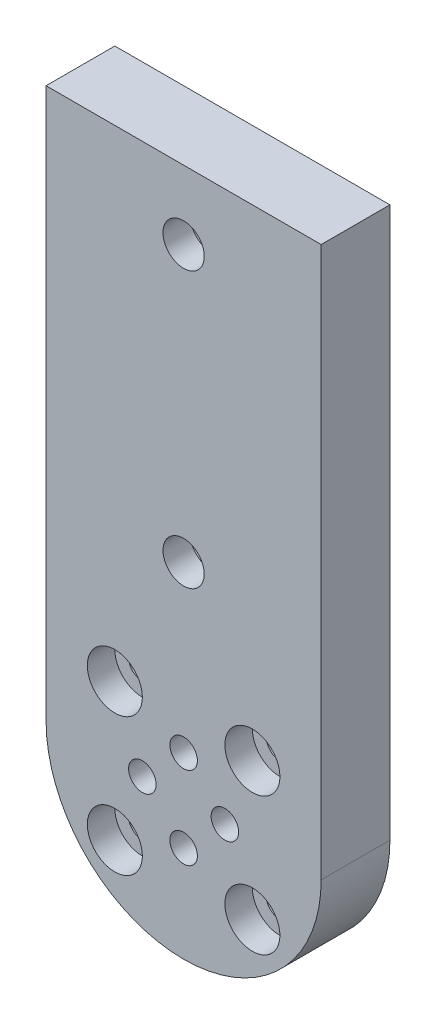
SolidWorks part; units mm, degrees
material "1060 Alloy"
ref_plane "Front Plane" through (0, 0, 0) normal (0, 0, 1) x (1, 0, 0)
ref_plane "Top Plane" through (0, 0, 0) normal (0, 1, 0) x (1, 0, 0)
ref_plane "Right Plane" through (0, 0, 0) normal (1, 0, 0) x (0, 0, -1)
sketch "Sketch2" plane through (0, 0, 0) normal (0, 0, 1) x (1, 0, 0)
  line L0 (-10, 0) -> (-10, 40)
  line L1 (-5, 5) -> (5, 5) construction
  line L2 (-5, 5) -> (-5, -5) construction
  line L3 (-5, -5) -> (5, -5) construction
  line L4 (5, 5) -> (5, -5) construction
  line L5 (-5, 5) -> (5, -5) construction
  line L6 (-5, -5) -> (5, 5) construction
  line L7 (10, 0) -> (10, 40)
  line L8 (-10, 40) -> (10, 40)
  line L9 (0, 40) -> (0, -10) construction
  circle A0 centre (0, 0) radius 10
  circle A1 centre (-5, 5) radius 1
  circle A2 centre (5, 5) radius 1
  circle A3 centre (-5, -5) radius 1
  circle A4 centre (5, -5) radius 1
  circle A5 centre (0, 35) radius 1.5
  circle A6 centre (0, 15) radius 1.5
  dimension "D4" = 2
  dimension "D5" = 2
  dimension "D6" = 2
  dimension "D7" = 2
  dimension "D9" = 3
  dimension "D10" = 3
  dimension "D13" = 20
  dimension "D2" = 10
  dimension "D3" = 10
  dimension "D8" = 40
  dimension "D11" = 20
  dimension "D12" = 5
extrude "Boss-Extrude1" add sketch "Sketch2" along normal blind 5 contours A6 A0 A4 A3 A2 A1 | A6 A0 L7 L8 L0 A5 region at (0, 23.8236, 0) region at (0, 0, 0)
sketch "Sketch5" plane through (0, 0, 5) normal (0, 0, 1) x (1, 0, 0)
  line L0 (-10, 0) -> (10, 0) construction
  line L1 (0, -13.5) -> (0, 13.5) construction
  circle A0 centre (-5, 5) radius 2
  circle A1 centre (5, 5) radius 2
  circle A2 centre (5, -5) radius 2
  circle A3 centre (-5, -5) radius 2
  circle A4 centre (0, 15) radius 1.5 construction
  circle A5 centre (0, 3) radius 1
  circle A6 centre (-3, 0) radius 1
  circle A7 centre (3, 0) radius 1
  circle A8 centre (0, -3) radius 1
  point P17 (0, 0)
  point P24 (0, 0)
  dimension "D1" = 4
  dimension "D2" = 4
  dimension "D3" = 4
  dimension "D4" = 4
  dimension "D5" = 2
  dimension "D10" = 2
  dimension "D11" = 2
  dimension "D12" = 2
  dimension "D6" = 3
  dimension "D7" = 3
  dimension "D8" = 3
  dimension "D9" = 3
extrude "Cut-Extrude2" cut sketch "Sketch5" against normal blind 2
sketch "Sketch6" plane through (0, 0, 0) normal (0, 0, -1) x (-1, 0, 0)
  line L0 (0, 40) -> (0, -10) construction
  circle A0 centre (0, 35) radius 3.5
  circle A1 centre (0, 15) radius 3.5
  dimension "D1" = 7
  dimension "D2" = 7
extrude "Cut-Extrude3" cut sketch "Sketch6" against normal blind 3
